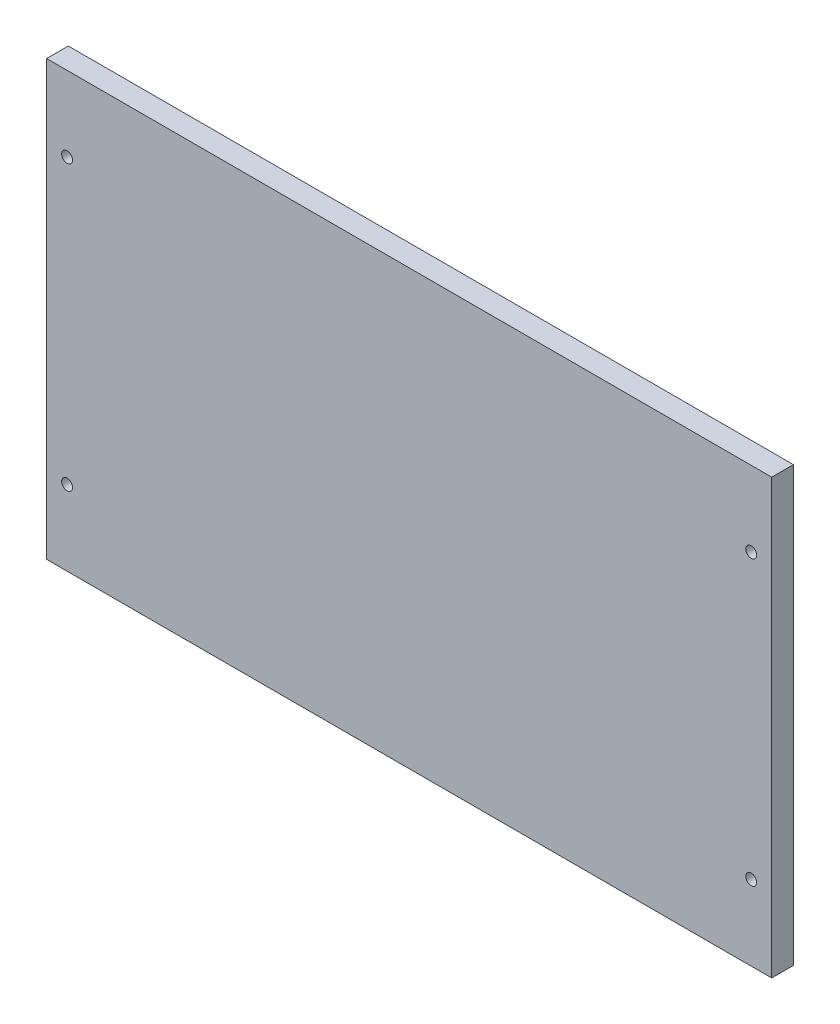
SolidWorks part; units mm, degrees
ref_plane "Front Plane" through (0, 0, 0) normal (0, 0, 1) x (1, 0, 0)
ref_plane "Top Plane" through (0, 0, 0) normal (0, 1, 0) x (1, 0, 0)
ref_plane "Right Plane" through (0, 0, 0) normal (1, 0, 0) x (0, 0, -1)
sketch "Sketch1" plane through (0, 0, 0) normal (0, 0, 1) x (1, 0, 0)
  line L0 (106.15, 127) -> (106.15, 0) construction
  line L1 (0, 0) -> (212.3, 0)
  line L2 (0, 0) -> (0, 127)
  line L3 (0, 127) -> (212.3, 127)
  line L4 (212.3, 0) -> (212.3, 127)
  line L5 (0, 63.5) -> (212.3, 63.5) construction
  circle A3 centre (6, 105) radius 1.6
  circle A7 centre (206.3, 105) radius 1.6
  circle A8 centre (206.3, 22) radius 1.6
  circle A9 centre (6, 22) radius 1.6
  dimension "D11" = 3.2
  dimension "D1" = 127
  dimension "D2" = 212.3
  dimension "D12" = 6
  dimension "D13" = 22
extrude "Wall" add sketch "Sketch1" along normal blind 6.35
sketch "Sketch2" [suppressed] plane through (0, 0, 6.35) normal (0, 0, 1) x (1, 0, 0)
  line L0 (106.15, 127) -> (106.15, 98.425) construction
  line L1 (212.3, 127) -> (0, 127) construction
  line L2 (106.15, 98.425) -> (70.7667, 98.425) construction
  line L3 (106.15, 98.425) -> (141.5333, 98.425) construction
  line L4 (0, 127) -> (0, 0) construction
  circle A0 centre (106.15, 98.425) radius 3.9687
  circle A1 centre (70.7667, 98.425) radius 3.9688
  circle A2 centre (141.5333, 98.425) radius 3.9687
  dimension "D2" = 7.9375
  dimension "D1" = 28.575
  dimension "D3" = 70.7667
extrude "RodSupportCutouts" [suppressed] cut sketch "Sketch2" against normal up to next
sketch "Sketch3" [suppressed] plane through (0, 0, 6.35) normal (0, 0, 1) x (1, 0, 0)
  line L1 (25.4, 88.9) -> (257.6, 88.9)
  line L2 (25.4, 88.9) -> (25.4, 114.3)
  line L3 (25.4, 114.3) -> (257.6, 114.3)
  line L4 (257.6, 88.9) -> (257.6, 114.3)
  line L5 (25.4, 88.9) -> (257.6, 114.3) construction
  line L6 (25.4, 114.3) -> (257.6, 88.9) construction
  line L7 (283, 127) -> (0, 127) construction
  line L8 (0, 127) -> (0, 0) construction
  point P0 (141.5, 101.6)
  point P9 (141.5, 127)
  dimension "D1" = 25.4
  dimension "D2" = 25.4
  dimension "D3" = 25.4
extrude "CannulaLargeCutout" [suppressed] cut sketch "Sketch3" against normal up to next
sketch "Sketch4" [suppressed] plane through (0, 0, 9.525) normal (0, 0, 1) x (1, 0, 0)
  line L0 (6, 103.5) -> (194, 103.5) construction
  line L1 (6, 105) -> (6, 22) construction
  line L2 (194, 105) -> (194, 22) construction
  line L3 (200, 127) -> (0, 127) construction
  line L4 (0, 127) -> (0, 0) construction
  circle A0 centre (60, 103.5) radius 6.35
  circle A1 centre (20, 103.5) radius 6.35
  circle A2 centre (100, 103.5) radius 6.35
  circle A3 centre (140, 103.5) radius 6.35
  circle A4 centre (60, 63.5) radius 6.35
  circle A5 centre (100, 63.5) radius 6.35
  circle A6 centre (140, 63.5) radius 6.35
  circle A7 centre (60, 23.5) radius 6.35
  circle A8 centre (100, 23.5) radius 6.35
  circle A9 centre (140, 23.5) radius 6.35
  circle A10 centre (20, 63.5) radius 6.35
  circle A11 centre (20, 23.5) radius 6.35
  circle A12 centre (180, 103.5) radius 6.35
  circle A13 centre (180, 63.5) radius 6.35
  circle A14 centre (180, 23.5) radius 6.35
  point P42 (100, 127)
  point P45 (0, 63.5)
  dimension "D3" = 12.7
  dimension "D1" = 5
  dimension "D2" = 3
extrude "CannulaHoles" [suppressed] cut sketch "Sketch4" against normal up to next
equation "\"Length\"= 283mm"
equation "\"Width\"= 225mm"
equation "\"WallThickness\"= 0.25in"
equation "\"UpperWaterJacketThickness\"= 28mm"
equation "\"SpacerHeight\"= 80.2mm"
equation "\"SpacerCornerWidth\"= 10mm"
equation "\"SpacerCornerHeight\"= 60.16mm"
equation "\"SpacerPegDiameter\"= 10mm"
equation "\"SpacerPegHeight\"= 10mm"
equation "\"TubingShort\"= 110mm"
equation "\"TubingLong\"= 175mm"
equation "\"PlateLength\"= 252mm"
equation "\"PlateWidth\"= 190mm"
equation "\"PlateHoleDiameter\"= 5.9mm"
equation "\"PlateHoleBottom\"= 2mm"
equation "\"PlateHoleSide\"= 1.55mm"
equation "\"PlateHoleSpacing\"= 3.1mm"
equation "\"PlateThickness\"= 1.55mm"
equation "\"ReservoirBottom\"= 12.5mm"
equation "\"ReservoirSupportWidth\"= 12mm"
equation "\"ReservoirSupportHeight\"= 15.1mm"
equation "\"ReservoirSupportPlacementHeight\"= 50mm"
equation "\"ReservoirHoleDiameter\"= 12.7mm"
equation "\"ReservoirHoleRight\"= 25mm"
equation "\"ReservoirHoleTop\"= \"ReservoirSupportPlacementHeight\""
equation "\"ReservoirHeight\"= 90mm"
equation "\"ReservoirPortBottom\"= 4mm"
equation "\"ReservoirPortTop\"= 10mm"
equation "\"ReservoirPortWidth\"= 101mm"
equation "\"CustomSpacerHeight\"= 5in"
equation "\"CustomSpacerRodHoleHeight\"= .75in"
equation "\"CustomSpacerRodHoleDiameter\"= .3125in"
equation "\"ScrewBlockSide\"= 12mm"
equation "\"ScrewBlockUpperHeight\"= 16mm"
equation "\"ScrewBlockLowerHeight\"= 16mm"
equation "\"InternalLength\"= \"Length\" - ( 2 * \"WallThickness\" )"
equation "\"InternalWidth\"= \"Width\" - ( 2 * \"WallThickness\" )"
equation "\"CustomSpacerPegHeight\"= 1in"
equation "\"CustomSpacerScrewBore\"=3.2mm"
equation "\"CustomSpacerScrewDepth\"=10mm"
equation "\"D1@Sketch1\"=\"CustomSpacerHeight\""
equation "\"D2@Sketch1\"=\"WallLength\""
equation "\"D11@Sketch1\"=\"CustomSpacerScrewBore\""
equation "\"D12@Sketch1\" = \"ScrewBlockSide\"/2"
equation "\"D13@Sketch1\"=\"ScrewBlockUpperHeight\"+\"ScrewBlockSide\"/2"
equation "\"D1@Wall\" = \"WallThickness\""
equation "\"D1@Sketch2\"=\"CustomSpacerRodHoleHeight\" + \"CustomSpacerRodHoleDiameter\" +0.0625in"
equation "\"D2@Sketch2\"=\"CustomSpacerRodHoleDiameter\""
equation "\"D3@Sketch2\"=\"InternalWidth\" / 3"
equation "\"D1@Sketch3\"=1in"
equation "\"WallLength\"= \"InternalWidth\""
